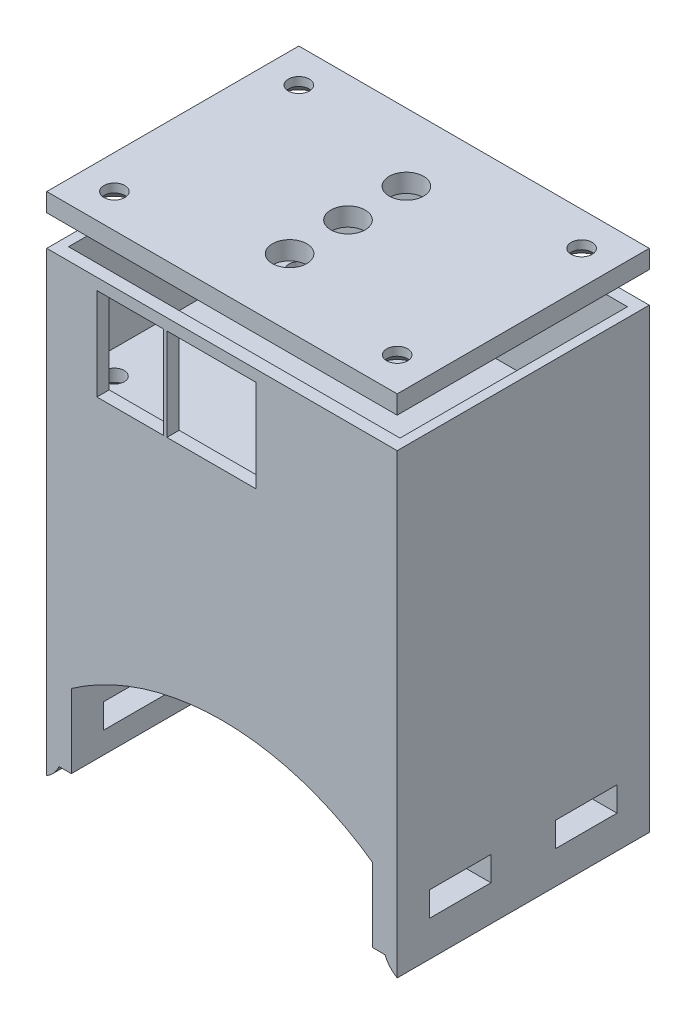
SolidWorks part; units mm, degrees
ref_plane "前视基准面" through (0, 0, 0) normal (0, 0, 1) x (1, 0, 0)
ref_plane "上视基准面" through (0, 0, 0) normal (0, 1, 0) x (1, 0, 0)
ref_plane "右视基准面" through (0, 0, 0) normal (1, 0, 0) x (0, 0, -1)
sketch "草图1" plane through (0, 0, 0) normal (0, 1, 0) x (1, 0, 0)
  line L5 (0, -17.5) -> (0, 17.5) construction
  line L6 (-26, 0) -> (26, 0) construction
  line L7 (-23, 15) -> (23, 15) construction
  line L8 (-23, 15) -> (-23, -15) construction
  line L9 (-23, -15) -> (23, -15) construction
  line L10 (23, 15) -> (23, -15) construction
  line L11 (0, -15) -> (0, 15) construction
  line L12 (-23, 0) -> (23, 0) construction
  circle A0 centre (-23, 15) radius 1.6
  circle A1 centre (-23, -15) radius 1.6
  circle A2 centre (23, -15) radius 1.6
  circle A3 centre (23, 15) radius 1.6
  point P0 (0, 0)
  point P4 (0, 0)
sketch "草图2" plane through (0, 0, 0) normal (0, 1, 0) x (1, 0, 0)
  line L0 (0, -17.5) -> (0, 17.5) construction
  line L1 (-28.5, 20.5) -> (28.5, 20.5)
  line L2 (-28.5, 20.5) -> (-28.5, -20.5)
  line L3 (-28.5, -20.5) -> (28.5, -20.5)
  line L4 (28.5, 20.5) -> (28.5, -20.5)
  line L5 (0, -20.5) -> (0, 20.5) construction
  line L6 (-28.5, 0) -> (28.5, 0) construction
  point P0 (0, 0)
extrude "凸台-拉伸1" add sketch "草图2" along normal blind 2
extrude "切除-拉伸1" cut sketch "草图1" along normal blind 2
sketch "草图4" plane through (0, 0, 0) normal (0, 1, 0) x (1, 0, 0)
  line L1 (-28.5, 20.5) -> (28.5, 20.5)
  line L2 (-28.5, 20.5) -> (-28.5, -20.5)
  line L3 (-28.5, -20.5) -> (28.5, -20.5)
  line L4 (28.5, 20.5) -> (28.5, -20.5)
  line L5 (0, -20.5) -> (0, 20.5) construction
  line L6 (-28.5, 0) -> (28.5, 0) construction
  line L9 (-26.9571, -18.5) -> (26.9571, -18.5)
  line L10 (-26.9571, -18.5) -> (-26.9571, 18.5)
  line L11 (-26.9571, 18.5) -> (26.9571, 18.5)
  line L12 (26.9571, -18.5) -> (26.9571, 18.5)
  line L13 (0, 18.5) -> (0, -18.5) construction
  line L14 (-26.9571, 0) -> (26.9571, 0) construction
  point P0 (0, 0)
  point P4 (0, 0)
extrude "凸台-拉伸2" add sketch "草图4" along normal blind 20
sketch "草图5" plane through (0, 0, 20.5) normal (0, 0, 1) x (1, 0, 0)
  line L0 (-28.5, 10) -> (-25.5, 10) construction
  line L1 (-28.5, 20) -> (-28.5, 0) construction
  line L2 (-7.4677, 4.1391) -> (4.0465, 4.1391) construction
  line L3 (4.0465, 0) -> (4.0465, 4.1391) construction
  line L4 (-28.5, 0) -> (28.5, 0) construction
  line L5 (4.0465, 4.1391) -> (-28.5, 4.1391) construction
  line L6 (4.0465, 4.1391) -> (4.0465, 15.1391) construction
  line L7 (4.0465, 15.1391) -> (-7.4677, 15.1391) construction
  line L8 (-7.4677, 15.1391) -> (-7.4677, 4.1391) construction
  line L9 (-19.3677, 15.1391) -> (-10.5111, 4.1391) construction
  line L10 (-10.5111, 4.1391) -> (-10.5111, 15.1391) construction
  line L11 (-10.5111, 15.1391) -> (-19.3677, 15.1391) construction
  line L12 (-19.3677, 15.1391) -> (-19.3677, 4.1391) construction
  line L13 (-19.3677, 4.1391) -> (-10.5111, 4.1391) construction
  line L18 (-7.4677, 15.1391) -> (4.0465, 4.1391) construction
  line L19 (-20.3394, 16.1391) -> (-9.5394, 16.1391)
  line L20 (-20.3394, 16.1391) -> (-20.3394, 3.1391)
  line L21 (-20.3394, 3.1391) -> (-9.5394, 3.1391)
  line L22 (-9.5394, 16.1391) -> (-9.5394, 3.1391)
  line L23 (-14.9394, 3.1391) -> (-14.9394, 16.1391) construction
  line L24 (-20.3394, 9.6391) -> (-9.5394, 9.6391) construction
  line L26 (-8.9606, 16.1391) -> (5.5394, 16.1391)
  line L27 (-8.9606, 16.1391) -> (-8.9606, 3.1391)
  line L28 (-8.9606, 3.1391) -> (5.5394, 3.1391)
  line L29 (5.5394, 16.1391) -> (5.5394, 3.1391)
  line L30 (-1.7106, 3.1391) -> (-1.7106, 16.1391) construction
  line L31 (-8.9606, 9.6391) -> (5.5394, 9.6391) construction
  line L32 (-20.3394, 16.1391) -> (-9.5394, 16.1391)
  line L33 (-20.3394, 16.1391) -> (-20.3394, 18.1391)
  line L34 (-20.3394, 18.1391) -> (-9.5394, 18.1391)
  line L35 (-9.5394, 16.1391) -> (-9.5394, 18.1391)
  line L36 (-8.9606, 16.1391) -> (5.5394, 16.1391)
  line L37 (-8.9606, 16.1391) -> (-8.9606, 18.1391)
  line L38 (-8.9606, 18.1391) -> (5.5394, 18.1391)
  line L39 (5.5394, 16.1391) -> (5.5394, 18.1391)
  point P5 (-15.7, 9.6808)
  point P13 (-14.9394, 9.6391)
  point P21 (-1.7106, 9.6391)
extrude "切除-拉伸2" cut sketch "草图5" against normal blind 18.5 contours L22 L19 L20 L21 | L19 L35 L34 L33 | L29 L26 L27 L28 | L26 L39 L38 L37 region at (-14.9394, 17.1391, 20.5) region at (-14.9394, 9.6391, 20.5) region at (-1.7106, 17.1391, 20.5) region at (-1.7106, 9.6391, 20.5)
sketch "草图6" plane through (0, 0, 0) normal (0, 1, 0) x (1, 0, 0)
  line L1 (-28.5, 20.5) -> (28.5, 20.5)
  line L2 (-28.5, 20.5) -> (-28.5, -20.5)
  line L3 (-28.5, -20.5) -> (28.5, -20.5)
  line L4 (28.5, 20.5) -> (28.5, -20.5)
  line L5 (0, -20.5) -> (0, 20.5) construction
  line L6 (-28.5, 0) -> (28.5, 0) construction
  point P0 (0, 0)
extrude "凸台-拉伸3" add sketch "草图6" along normal blind 3 from offset 25
extrude "切除-拉伸4" cut sketch "草图1<2>" against normal blind 5 from surface starting at face at (0, 28, 0)
sketch "草图1<2>" plane through (0, 0, 0) normal (0, 1, 0) x (1, 0, 0) same geometry as "草图1"
sketch "草图7" plane through (0, 25, 0) normal (0, -1, 0) x (1, 0, 0)
  line L0 (-28.5, 20.5) -> (28.5, -20.5) construction
  circle A0 centre (0, 0) radius 2.8
  circle A3 centre (0, -9.5) radius 2.8
  circle A4 centre (0, 9.5) radius 2.8
  dimension "D1" = 2
  dimension "D2" = 2
extrude "切除-拉伸5" cut sketch "草图7" against normal blind 4
sketch "草图8" plane through (-28.5, 0, 0) normal (-1, 0, 0) x (0, 0, 1)
  line L0 (-20.5, 20) -> (20.5, 20) construction
  line L1 (-13.5982, 20) -> (-8.5982, 20)
  line L2 (-13.5982, 20) -> (-13.5982, 15)
  line L3 (-13.5982, 15) -> (-8.5982, 15)
  line L4 (-8.5982, 20) -> (-8.5982, 15)
extrude "切除-拉伸6" cut sketch "草图8" against normal blind 10
sketch "草图9" plane through (0, 0, 0) normal (0, -1, 0) x (1, 0, 0)
  line L1 (-28.5, 20.5) -> (28.5, 20.5)
  line L2 (-28.5, 20.5) -> (-28.5, -20.5)
  line L3 (-28.5, -20.5) -> (28.5, -20.5)
  line L4 (28.5, 20.5) -> (28.5, -20.5)
extrude "凸台-拉伸4" add sketch "草图9" along normal blind 40
sketch "草图10" plane through (0, 2, 0) normal (0, 1, 0) x (1, 0, 0)
  circle A0 centre (-23, 15) radius 1.4
  circle A1 centre (-23, -15) radius 1.4
  circle A2 centre (23, -15) radius 1.4
  circle A3 centre (23, 15) radius 1.4
extrude "切除-拉伸7" cut sketch "草图10" against normal blind 10
sketch "草图12" plane through (0, -40, 0) normal (0, -1, 0) x (1, 0, 0)
  line L0 (-28.5, -20.5) -> (28.5, -20.5) construction
  line L1 (-28.5, 20.5) -> (-20.5, 20.5)
  line L2 (-28.5, 20.5) -> (-28.5, -20.5)
  line L3 (-28.5, -20.5) -> (-20.5, -20.5)
  line L4 (-20.5, 20.5) -> (-20.5, -20.5)
  line L5 (28.5, 20.5) -> (-28.5, 20.5) construction
  line L6 (28.5, -20.5) -> (20.5, -20.5)
  line L7 (28.5, -20.5) -> (28.5, 20.5)
  line L8 (28.5, 20.5) -> (20.5, 20.5)
  line L9 (20.5, -20.5) -> (20.5, 20.5)
extrude "凸台-拉伸5" add sketch "草图12" along normal blind 15
sketch "草图13" plane through (0, -55, 0) normal (0, -1, 0) x (1, 0, 0)
  line L1 (-20.5, 20.5) -> (-24.5, 20.5)
  line L2 (-20.5, 20.5) -> (-20.5, -20.5)
  line L3 (-20.5, -20.5) -> (-24.5, -20.5)
  line L4 (-24.5, 20.5) -> (-24.5, -20.5)
  line L5 (20.5, 20.5) -> (24.5, 20.5)
  line L6 (20.5, 20.5) -> (20.5, -20.5)
  line L7 (20.5, -20.5) -> (24.5, -20.5)
  line L8 (24.5, 20.5) -> (24.5, -20.5)
extrude "切除-拉伸8" cut sketch "草图13" against normal blind 15
sketch "草图14" plane through (0, -55, 0) normal (0, -1, 0) x (1, 0, 0)
  line L1 (-24.5, 20.5) -> (-26.5, 20.5)
  line L2 (-24.5, 20.5) -> (-24.5, -20.5)
  line L3 (-24.5, -20.5) -> (-26.5, -20.5)
  line L4 (-26.5, 20.5) -> (-26.5, -20.5)
  line L5 (24.5, 20.5) -> (26.5, 20.5)
  line L6 (24.5, 20.5) -> (24.5, -20.5)
  line L7 (24.5, -20.5) -> (26.5, -20.5)
  line L8 (26.5, 20.5) -> (26.5, -20.5)
extrude "切除-拉伸9" cut sketch "草图14" against normal blind 3
sketch "草图15" plane through (-28.5, 0, 0) normal (-1, 0, 0) x (0, 0, 1)
  line L1 (-15.25, -44.9393) -> (-5.25, -44.9393)
  line L2 (-10.25, -48.5) -> (-10.25, -45.3787) construction
  line L3 (-15.25, -44.9393) -> (-15.25, -48.9393)
  line L4 (-15.25, -48.9393) -> (-5.25, -48.9393)
  line L5 (-5.25, -44.9393) -> (-5.25, -48.9393)
  line L6 (10.25, -48.5) -> (10.25, -44.4925) construction
  line L7 (-10.25, -48.9393) -> (-10.25, -44.9393) construction
  line L8 (-15.25, -46.9393) -> (-5.25, -46.9393) construction
  line L9 (5.25, -44.4962) -> (15.25, -44.4962)
  line L10 (5.25, -44.4962) -> (5.25, -48.4962)
  line L11 (5.25, -48.4962) -> (15.25, -48.4962)
  line L12 (15.25, -44.4962) -> (15.25, -48.4962)
  line L13 (10.25, -48.4962) -> (10.25, -44.4962) construction
  line L14 (5.25, -46.4962) -> (15.25, -46.4962) construction
  point P0 (-10.25, -46.9393)
  point P7 (10.25, -46.4962)
extrude "切除-拉伸10" cut sketch "草图15" against normal through all
sketch "草图19" plane through (0, 0, -20.5) normal (0, 0, -1) x (-1, 0, 0)
  line L0 (-24.5, -40) -> (24.5, -40)
  circle A0 centre (0, -74.7113) radius 42.4868
  line M12 (-24.5, -40) -> (24.5, -40)
extrude "切除-拉伸12" cut sketch "草图19" against normal through all contours A0 M12 region at (0, -36.8641, -20.5)
sketch "草图20" plane through (0, 0, -20.5) normal (0, 0, -1) x (-1, 0, 0)
  line L0 (-26.5, -52) -> (-28.5, -55)
  line L1 (-28.5, -55) -> (-26.5, -55)
  line L2 (-26.5, -52) -> (-26.5, -55) construction
  line L3 (-26.5, -55) -> (-28.5, -55) construction
  line L4 (-26.5, -55) -> (-26.5, -52)
  line L5 (28.5, -55) -> (26.5, -52)
  line L6 (26.5, -52) -> (26.5, -55)
  line L7 (26.5, -55) -> (28.5, -55)
hole_wizard "M3 十字槽沉头木螺钉的锥形沉头孔1" positions "3D草图1" profile "草图21" countersink size "M3" standard "GB" end condition through all
sketch3d "3D草图1"
  line L0 (-23, 25, 15) -> (-23, 28, 15) construction
  line L1 (-23, 25, -15) -> (-23, 28, -15) construction
  line L2 (23, 25, -15) -> (23, 28, -15) construction
  line L3 (23, 25, 15) -> (23, 28, 15) construction
  point P0 (-23, 25, 15)
  point P4 (-23, 25, -15)
  point P8 (23, 25, -15)
  point P12 (23, 25, 15)
sketch "草图21" plane through (-23, 25, 15) normal (1, 0, 0) x (0, 0, -1)
  line L0 (0, 0) -> (0, 3)
  line L1 (0, 3) -> (1.7, 3)
  line L2 (1.7, 3) -> (1.7, 1.6)
  line L3 (1.7, 1.6) -> (3.3, 0)
  line L5 (3.3, 0) -> (0, 0)
  line L6 (-1.7, 1.6) -> (-3.3, 0) construction
  line L11 (0, -6.35) -> (0, 107.95) construction
  dimension "通孔孔直径" = 3.4
  dimension "通孔孔深度" = 3
  dimension "近端锥形沉头孔直径" = 6.6
  dimension "近端锥形沉头孔角度" = 90
fillet "圆角1" radius 5 2 edges at (26.5, -55, 0) (-26.5, -55, 0)
